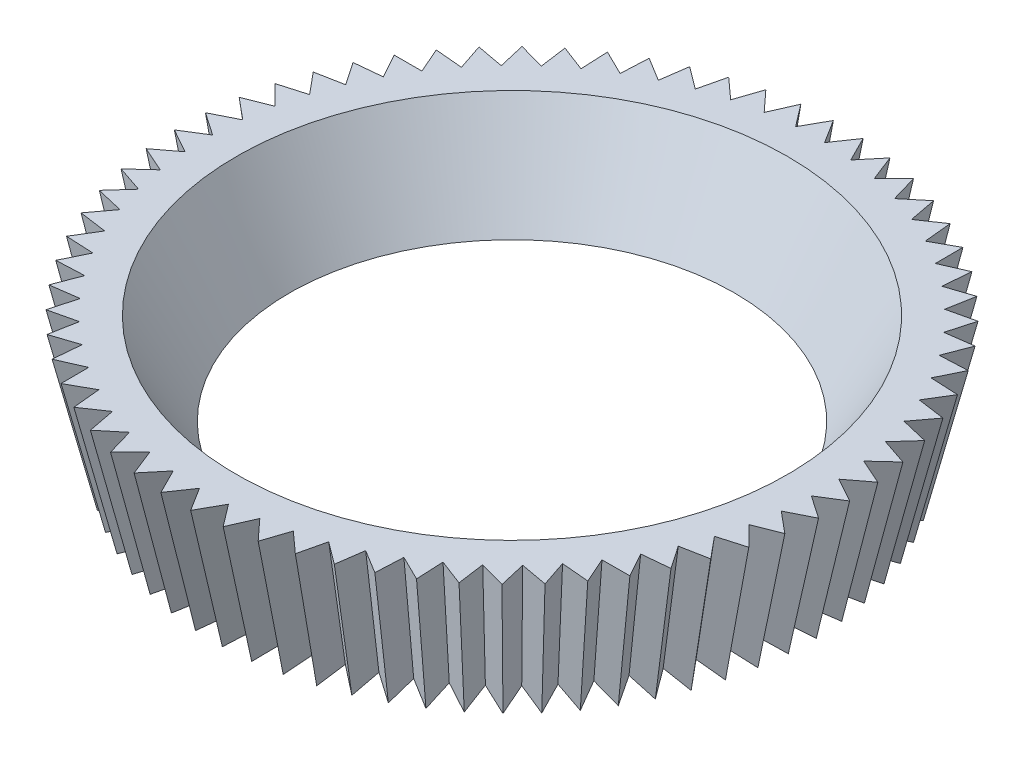
SolidWorks part; units mm, degrees
ref_plane "Front Plane" through (0, 0, 0) normal (0, 0, 1) x (1, 0, 0)
ref_plane "Top Plane" through (0, 0, 0) normal (0, 1, 0) x (1, 0, 0)
ref_plane "Right Plane" through (0, 0, 0) normal (1, 0, 0) x (0, 0, -1)
sketch "Sketch1" plane through (0, 0, 0) normal (0, 0, 1) x (1, 0, 0)
  line L1 (7.0245, 11.8104) -> (8, 13.5)
  line L2 (5.25, 12.8349) -> (6.5, 15)
  line L4 (0, 11.8104) -> (7.0245, 11.8104) construction
  line L5 (0, 11.8104) -> (0, 15) construction
  line L6 (7.0245, 11.8104) -> (5.25, 12.8349)
  line L9 (8, 13.5) -> (8, 15)
  line L10 (8, 15) -> (6.5, 15)
  point P3 (3.8102, 11.8914)
  dimension "D1" = 8
  dimension "D2" = 120
  dimension "D3" = 15
  dimension "D4" = 1.5
  dimension "D5" = 1.5
  dimension "D6" = 2.5
revolve "Revolve1" add sketch "Sketch1" angle 360 about L5
sketch "Sketch2" plane through (0, 15, 0) normal (0, 1, 0) x (1, 0, 0)
  line L0 (0.0657, -7.9997) -> (0.5115, -7.2015)
  line L1 (0.5115, -7.2015) -> (1.0657, -7.9287)
  arc A0 (0.0657, -7.9997) -> (1.0657, -7.9287) centre (0, 0) ccw
  circle A1 centre (0, 0) radius 8 construction
  dimension "D1" = 1
extrude "Cut-Extrude1" cut sketch "Sketch2" against normal through all draft 7 draft outward yes
pattern_circular "CirPattern1" count 68 over 360 about axis through (0, 15, 0) along (0, -1, 0) of "Cut-Extrude1"
